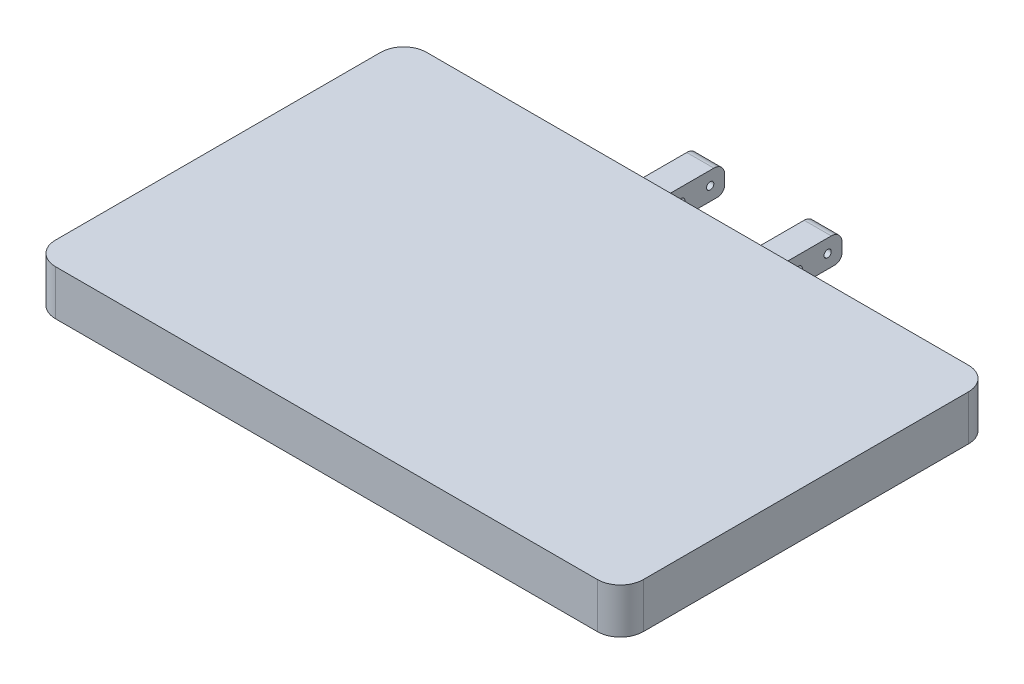
SolidWorks part; units mm, degrees
material "AISI 347 Annealed Stainless Steel (SS)"
ref_plane "Front Plane" through (0, 0, 0) normal (0, 0, 1) x (1, 0, 0)
ref_plane "Top Plane" through (0, 0, 0) normal (0, 1, 0) x (1, 0, 0)
ref_plane "Right Plane" through (0, 0, 0) normal (1, 0, 0) x (0, 0, -1)
sketch "Sketch1" plane through (0, 0, 0) normal (0, 1, 0) x (1, 0, 0)
  line L0 (0, 0) -> (381, 0)
  line L1 (397.1798, 16.1798) -> (397.1798, 244.7798)
  line L2 (397.1798, 130.4798) -> (0, 130.4798) construction
  line L3 (0, 260.9596) -> (381, 260.9596)
  line L4 (190.5, 260.9596) -> (190.5, 0) construction
  line L5 (-16.1798, 16.1798) -> (-16.1798, 244.7798)
  line L6 (139.7, 260.9596) -> (139.7, 311.7596)
  line L7 (139.7, 311.7596) -> (241.3, 311.7596)
  line L8 (241.3, 311.7596) -> (241.3, 260.9596)
  arc A0 (381, 0) -> (397.1798, 16.1798) centre (381, 16.1798) ccw
  arc A1 (381, 260.9596) -> (397.1798, 244.7798) centre (381, 244.7798) cw
  arc A2 (0, 0) -> (-16.1798, 16.1798) centre (0, 16.1798) cw
  arc A3 (0, 260.9596) -> (-16.1798, 244.7798) centre (0, 244.7798) ccw
  dimension "D1" = 16.1798
  dimension "D2" = 381
  dimension "D3" = 228.6
  dimension "D4" = 50.8
  dimension "D5" = 50.8
  dimension "D6" = 50.8
extrude "Boss-Extrude1" add sketch "Sketch1" along normal blind 31.75 contours L3 A3 L5 A2 L0 A0 L1 A1 region at (190.5, 0, -130.4798)
shell "Shell1" thickness 7.62 removed face at (190.5, 0, -130.4798)
extrude "Boss-Extrude3" add sketch "Sketch1<5>" along normal blind 19.05 contours L8 L7 L6 L3 region at (190.5, 0, -286.3596)
sketch "Sketch1<5>" plane through (0, 0, 0) normal (0, 1, 0) x (1, 0, 0) same geometry as "Sketch1"
sketch "Sketch4" plane through (0, 19.05, 0) normal (0, 1, 0) x (1, 0, 0)
  line L0 (139.7, 311.7596) -> (241.3, 311.7596) construction
  line L1 (158.75, 311.7596) -> (222.25, 311.7596)
  line L2 (158.75, 311.7596) -> (158.75, 260.9596)
  line L3 (158.75, 260.9596) -> (222.25, 260.9596)
  line L4 (222.25, 311.7596) -> (222.25, 260.9596)
  line L5 (139.7, 260.9596) -> (241.3, 260.9596) construction
  line L6 (139.7, 260.9596) -> (139.7, 311.7596) construction
  line L7 (241.3, 311.7596) -> (241.3, 260.9596) construction
  dimension "D1" = 19.05
  dimension "D2" = 19.05
extrude "Cut-Extrude2" cut sketch "Sketch4" against normal through all both and the other way through all
fillet "Fillet5" radius 7.62 1 edges at (231.775, 19.05, -311.7596)
fillet "Fillet6" radius 5.08 1 edges at (231.775, 0, -311.7596)
fillet "Fillet7" radius 7.62 1 edges at (149.225, 19.05, -311.7596)
fillet "Fillet8" radius 5.08 1 edges at (149.225, 0, -311.7596)
fillet "Fillet9" radius 5.08 1 edges at (231.775, 19.05, -260.9596)
fillet "Fillet10" radius 5.08 1 edges at (149.225, 19.05, -260.9596)
fillet "Fillet11" radius 2.54 1 edges at (241.3, 12.065, -260.9596)
fillet "Fillet12" radius 2.54 1 edges at (222.25, 12.065, -260.9596)
fillet "Fillet13" radius 2.54 1 edges at (158.75, 12.065, -260.9596)
fillet "Fillet14" radius 2.54 1 edges at (139.7, 12.065, -260.9596)
sketch "Sketch5" plane through (241.3, 0, 0) normal (1, 0, 0) x (0, 0, -1)
  line L0 (304.1396, 19.05) -> (266.0396, 19.05) construction
  line L1 (311.7596, 11.43) -> (311.7596, 5.08) construction
  circle A0 centre (301.5996, 9.525) radius 2.54
  circle A1 centre (281.2796, 9.525) radius 2.54
  dimension "D1" = 5.08
  dimension "D2" = 5.08
  dimension "D3" = 9.525
  dimension "D4" = 9.525
  dimension "D5" = 30.48
  dimension "D6" = 10.16
extrude "Cut-Extrude3" cut sketch "Sketch5" against normal through all both and the other way through all
